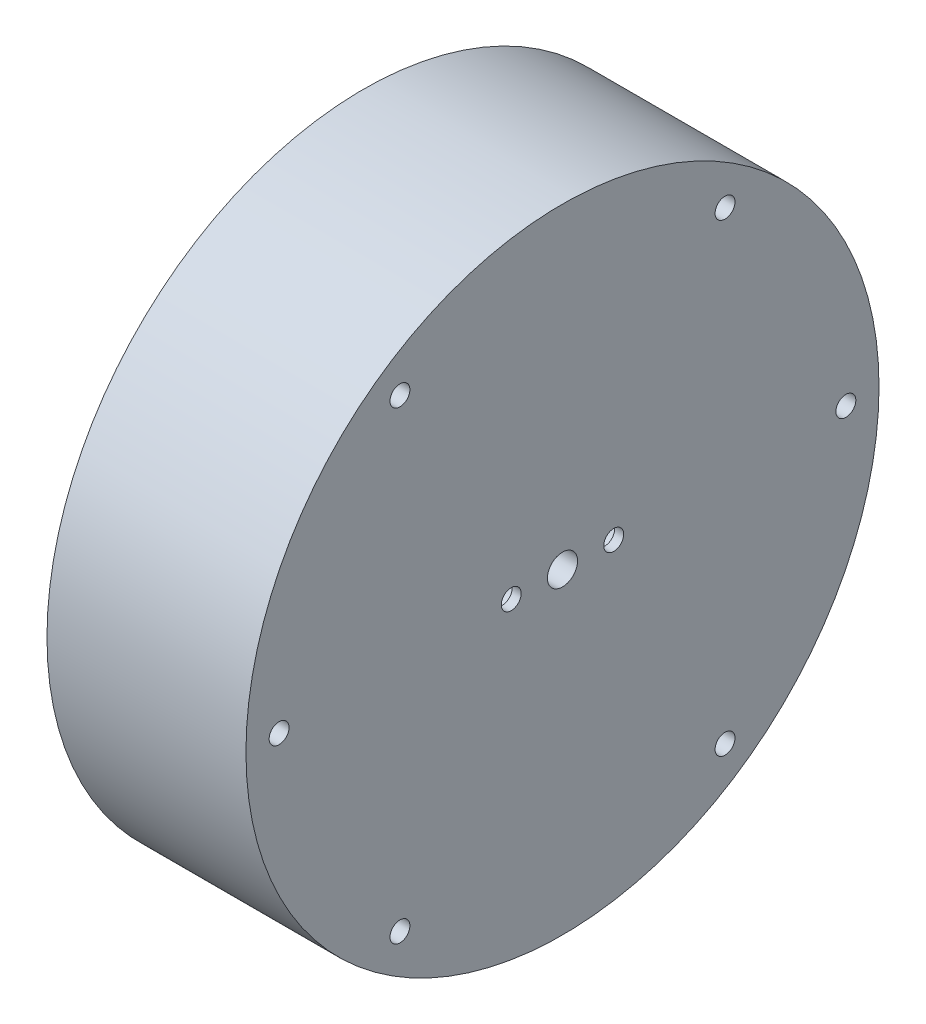
SolidWorks part; units mm, degrees
ref_plane "Plane1" through (0, 0, 0) normal (0, 0, 1) x (1, 0, 0)
ref_plane "Plane2" through (0, 0, 0) normal (0, 1, 0) x (1, 0, 0)
ref_plane "Plane3" through (0, 0, 0) normal (1, 0, 0) x (0, 0, -1)
sketch "HoldingSke" plane through (0, 0, 0) normal (0, 1, 0) x (1, 0, 0)
  line L0 (0, 0) -> (0.0872, -0.9962)
  line L1 (-15, 0) -> (100, 0) construction
  line L2 (0, 0) -> (-2.1039, 2.3779)
  line L3 (0, 0) -> (-11.863, 4.5341)
  line L4 (0, 0) -> (0.7527, 8.6031)
  line L5 (0, 0) -> (-23.7986, -8.8762)
  line L6 (0, 0) -> (-10.5278, -7.1032)
  line L7 (-2.1039, 2.3779) -> (3.3635, 27.1825)
  line L8 (-76.2, 3.3779) -> (-54.61, 3.3779)
  line L9 (-71.009, 38.7566) -> (-53.1078, 45.2721)
  line L10 (-76.2, 71.12) -> (104.1128, 71.12)
  line L11 (0, 0) -> (-15, 0)
  line L12 (-76.2, 101.6) -> (-76.162, 101.6)
  line L13 (24.9733, 27.94) -> (52.9518, 28.4284)
  line L14 (24.9733, 27.94) -> (24.9743, 27.94)
  line L15 (24.9733, 27.94) -> (100.4006, 29.5858)
  circle A0 centre (0, 0) radius 50
  circle A1 centre (0, 0) radius 12.7
  circle A2 centre (0, 0) radius 12.7
  dimension "MHD" = 25.4
  dimension "Hub_dia" = 25.4
  dimension "Diameter" = 100
  dimension "Num_teeth" = 85
  dimension "Pitch" = 1
  dimension "Overall_len" = 25.4
  dimension "Show_teeth" = 85
  dimension "Thickness" = 12.7
  dimension "OAL" = 25.4001
  dimension "T_dim" = 21.59
  dimension "Ap" = 20
  dimension "H" = 19.05
  dimension "Pitch_radius" = 180.3128
  dimension "Width" = 15
  dimension "Backlash" = 0.038
  dimension "Addendum_fac" = 1
  dimension "Dedendum_fac" = 1.25
  dimension "Clearance_fac" = 0.25
  dimension "Dedendum_add" = 0.001
  dimension "Module" = 1
sketch "BasProSke" plane through (0, 0, 0) normal (0, 1, 0) x (1, 0, 0)
  line L0 (-10, 0) -> (60, 0) construction
  line L1 (0, 41.5) -> (0, 50)
  line L2 (0, 41.5) -> (15, 41.5)
  line L3 (15, 41.5) -> (15, 50)
  line L4 (15, 50) -> (0, 50)
  dimension "Diameter" = 100
  dimension "Thickness" = 15
  dimension "Inside_diameter" = 83
revolve "Base-Revolve" add sketch "BasProSke" angle 360 about L0
sketch "TooCutSke" plane through (0, 0, 0) normal (1, 0, 0) x (0, 0, -1)
  line L3 (0.8804, 42.4909) -> (0.8804, 53.6633) construction
  line L4 (0, 0) -> (0, 59.563) construction
  line L5 (0, 0) -> (-2.5248, 68.2808) construction
  line L6 (-19.1021, 35.2615) -> (36.4888, 37.317) construction
  circle A0 centre (0, 0) radius 42.5 construction
  circle A1 centre (0, 0) radius 43.751 construction
  circle A2 centre (0, 0) radius 35.9432 construction
  circle A3 centre (0, 0) radius 41.4746 construction
  arc A4 (1.2248, 41.4565) -> (0.3791, 43.7494) centre (-19.1021, 35.2615) ccw
  arc A5 (1.2248, 41.4565) -> (-1.2248, 41.4565) centre (0, 0) ccw
  arc A6 (0.3791, 43.7494) -> (-0.3791, 43.7494) centre (0, 0) ccw
  arc A7 (-0.3791, 43.7494) -> (-1.2248, 41.4565) centre (19.1021, 35.2615) ccw
  dimension "Pitch_dia" = 85
  dimension "Base_dia" = 71.8865
  dimension "Root_dia" = 87.502
  dimension "Overcut_dia" = 82.9492
  dimension "Flank_rad" = 21.25
  dimension "Half_ang" = 2.118
  dimension "Half_CT" = 0.8804
extrude "ToothCut" cut sketch "TooCutSke" along normal through all
fillet "Breaks" [suppressed] radius 0.1
fillet "RootFillets" [suppressed] radius 0.251
pattern_circular "TeethCuts" count 85 every 4.235 about axis through (-10, 0, 0) along (1, 0, 0) of "RootFillets", "Breaks", "ToothCut"
sketch "Sketch1" plane through (15, 0, 0) normal (1, 0, 0) x (0, 0, -1)
  circle A0 centre (0, 0) radius 52.5
  dimension "D1" = 105
extrude "Boss-Extrude1" add sketch "Sketch1" along normal blind 4
sketch "Sketch2" plane through (19, 0, 0) normal (1, 0, 0) x (0, 0, -1)
  circle A0 centre (0, 0) radius 2.5
  dimension "D1" = 5
extrude "Cut-Extrude1" cut sketch "Sketch2" against normal blind 4
sketch "Sketch3" plane through (19, 0, 0) normal (1, 0, 0) x (0, 0, -1)
  line L0 (0, 0) -> (-8.5, 0) construction
  line L1 (0, 0) -> (8.5, 0) construction
  circle A0 centre (-8.5, 0) radius 1.65
  circle A1 centre (8.5, 0) radius 1.65
  dimension "D2" = 3.3
  dimension "D1" = 8.5
extrude "Cut-Extrude2" cut sketch "Sketch3" against normal blind 4
sketch "Sketch4" plane through (15, 0, 0) normal (-1, 0, 0) x (0, 0, 1)
  circle A0 centre (-8.5, 0) radius 2.75
  circle A1 centre (8.5, 0) radius 2.75
  dimension "D1" = 5.5
extrude "Cut-Extrude3" cut sketch "Sketch4" against normal blind 2.5
sketch "Sketch6" plane through (0, 0, 0) normal (-1, 0, 0) x (0, 0, 1)
  circle A0 centre (0, 0) radius 50
  circle A2 centre (0, 0) radius 39.55
extrude "Boss-Extrude3" add sketch "Sketch6" along normal blind 4
sketch "Sketch7" plane through (-4, 0, 0) normal (-1, 0, 0) x (0, 0, 1)
  circle A0 centre (0, 0) radius 50
  circle A1 centre (0, 0) radius 42.5
  dimension "D1" = 7.5
extrude "Boss-Extrude4" add sketch "Sketch7" along normal blind 10
sketch "Sketch8" plane through (-14, 0, 0) normal (-1, 0, 0) x (0, 0, 1)
  line L0 (0, 0) -> (-47, 0) construction
  line L1 (0, 0) -> (-47, 0) construction
  line L2 (0, 0) -> (-26.9581, 38.5001) construction
  line L3 (0, 0) -> (-26.9581, -38.5001) construction
  line L4 (0, 0) -> (47, 0) construction
  line L5 (0, 0) -> (26.9581, -38.5001) construction
  line L6 (0, 0) -> (26.9581, 38.5001) construction
  line L7 (-47, 0) -> (47, 0) construction
  circle A1 centre (-47, 0) radius 1.65
  circle A2 centre (-26.9581, 38.5001) radius 1.65
  circle A3 centre (-26.9581, -38.5001) radius 1.65
  circle A4 centre (47, 0) radius 1.65
  circle A5 centre (26.9581, 38.5001) radius 1.65
  circle A6 centre (26.9581, -38.5001) radius 1.65
  dimension "D1" = 47
  dimension "D3" = 3.3
  dimension "D2" = 55
  dimension "D4" = 55
  dimension "D5" = 55
  dimension "D6" = 55
sketch "Sketch9" plane through (15, 0, 0) normal (-1, 0, 0) x (0, 0, 1)
  circle A0 centre (0, 0) radius 50
  circle A1 centre (0, 0) radius 52.5
extrude "Boss-Extrude5" add sketch "Sketch9" along normal up to surface (29 mm away) up to face at (-14, 0, 50)
extrude "Cut-Extrude4" cut sketch "Sketch8" against normal through all
equation "' \"Module@HoldingSke\" = 6.35"
equation "' \"Num_teeth@HoldingSke\" = 24"
equation "' \"Ap@HoldingSke\" =  14.5"
equation "' \"Ap@HoldingSke\" = 14.5"
equation "' \"Width@HoldingSke\" = 12"
equation "' \"Diameter@HoldingSke\" = 8 * 25.4"
equation "' \"Show_teeth@HoldingSke\" = 100"
equation "' \"Backlash@HoldingSke\" = 0.009 * 25.4"
equation "' \"Addendum_fac@HoldingSke\" = 1.0"
equation "' \"Dedendum_fac@HoldingSke\" = 1.25"
equation "' \"Dedendum_add@HoldingSke\" = 0.00005 * 25.4"
equation "' \"Clearance_fac@HoldingSke\" = 0.25"
equation "\"Pitch@HoldingSke\" = 1 / \"Module@HoldingSke\" "
equation "\"Overcut_dia@TooCutSke\" = (\"Num_teeth@HoldingSke\" - 2 * \"Addendum_fac@HoldingSke\") / \"Pitch@HoldingSke\" - 0.002 * 25.4"
equation "\"Pitch_dia@TooCutSke\" = \"Num_teeth@HoldingSke\" / \"Pitch@HoldingSke\""
equation "\"Base_dia@TooCutSke\" = \"Num_teeth@HoldingSke\" / \"Pitch@HoldingSke\" * cos((\"Ap@HoldingSke\"  * 3.14159265 / 180)) * 0.90"
equation "\"Root_dia@TooCutSke\" = \"Num_teeth@HoldingSke\"  / \"Pitch@HoldingSke\" + 2 *  \"Dedendum_fac@HoldingSke\"/ \"Pitch@HoldingSke\" + \"Dedendum_add@HoldingSke\" * 2"
equation "\"Half_ang@TooCutSke\" = 180 / \"Num_teeth@HoldingSke\""
equation "\"Half_CT@TooCutSke\" = \"Num_teeth@HoldingSke\" / \"Pitch@HoldingSke\" * sin((3.14159265 / 2 / \"Num_teeth@HoldingSke\")) / 2 + 10 * \"Backlash@HoldingSke\" / 4"
equation "\"Flank_rad@TooCutSke\" = \"Num_teeth@HoldingSke\" / \"Pitch@HoldingSke\" / 4"
equation "\"Radius@RootFillets\"= \"Clearance_fac@HoldingSke\" / \"Pitch@HoldingSke\" + \"Dedendum_add@HoldingSke\""
equation "\"Break_rad@Breaks\" = 0.02 / \"Pitch@HoldingSke\" * 5"
equation "\"Num_teeth@TeethCuts\" = int( \"Show_teeth@HoldingSke\" ) + 1"
equation "\"Num_teeth@TeethCuts\" = ((sgn( \"Num_teeth@TeethCuts\" - \"Num_teeth@HoldingSke\" )-1)*( \"Num_teeth@TeethCuts\" - \"Num_teeth@HoldingSke\" ))/-2+ \"Num_teeth@HoldingSke\""
equation "\"Num_teeth@TeethCuts\" = ((sgn( \"Num_teeth@TeethCuts\" - 2.0)+1)*( \"Num_teeth@TeethCuts\" - 2.0))/2 +2.0"
equation "\"Angle@TeethCuts\" = 360.0 / \"Num_teeth@HoldingSke\""
equation "\"Diameter@BasProSke\" = \"Num_teeth@HoldingSke\"  / \"Pitch@HoldingSke\" + 2 *  \"Dedendum_fac@HoldingSke\"/ \"Pitch@HoldingSke\" + \"Dedendum_add@HoldingSke\" * 2 + 0.002 * 25.4"
equation "\"Diameter@BasProSke\" = ((sgn( \"Diameter@BasProSke\"  - \"Diameter@HoldingSke\" )+1)*( \"Diameter@BasProSke\"  - \"Diameter@HoldingSke\" ))/2 + \"Diameter@HoldingSke\""
equation "\"Inside_diameter@BasProSke\" =  (\"Num_teeth@HoldingSke\" - 2 * \"Addendum_fac@HoldingSke\") / \"Pitch@HoldingSke\" "
equation "\"Thickness@BasProSke\"  = \"Width@HoldingSke\""
